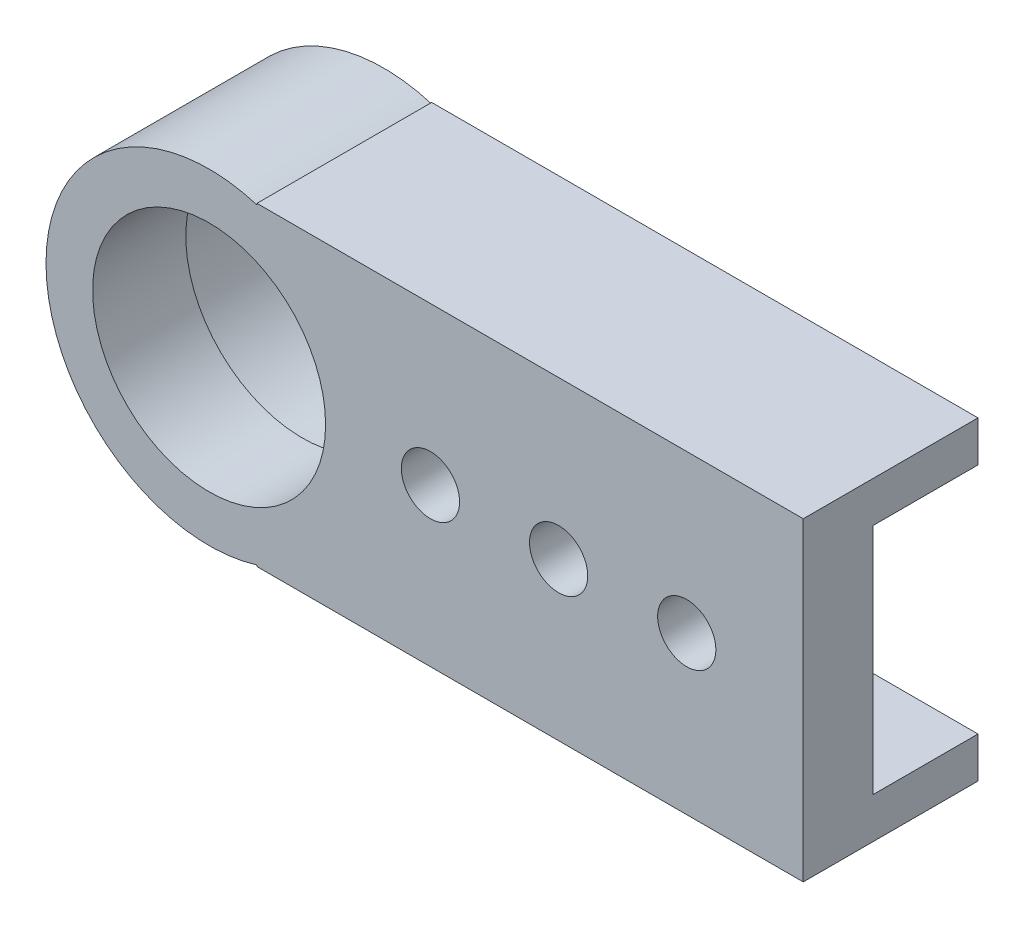
SolidWorks part; units mm, degrees
ref_plane "前视基准面" through (0, 0, 0) normal (0, 0, 1) x (1, 0, 0)
ref_plane "上视基准面" through (0, 0, 0) normal (0, 1, 0) x (1, 0, 0)
ref_plane "右视基准面" through (0, 0, 0) normal (1, 0, 0) x (0, 0, -1)
sketch "草图1" plane through (0, 0, 0) normal (0, 0, 1) x (1, 0, 0)
  line L1 (20, -10) -> (-20, -10)
  line L2 (20, -10) -> (20, 10)
  line L3 (20, 10) -> (-20, 10)
  line L4 (-20, -10) -> (-20, 10)
  line L5 (20, -10) -> (-20, 10) construction
  line L6 (20, 10) -> (-20, -10) construction
  point P0 (0, 0)
  dimension "D1" = 40
  dimension "D2" = 20
extrude "凸台-拉伸1" add sketch "草图1" along normal blind 6
sketch "草图2" plane through (0, 0, 6) normal (0, 0, 1) x (1, 0, 0)
  line L0 (20, -10) -> (20, 10) construction
  circle A0 centre (10, 0) radius 2.5
  circle A1 centre (-1, 0) radius 2.5
  circle A2 centre (-12, 0) radius 2.5
  dimension "D1" = 10
  dimension "D2" = 5
  dimension "D3" = 3
extrude "切除-拉伸1" cut sketch "草图2" against normal through all
sketch "草图3" plane through (0, 0, 6) normal (0, 0, 1) x (1, 0, 0)
  line L0 (20, 13.5) -> (20, 10)
  line L1 (20, -13.5) -> (-26.894, -13.5)
  line L3 (20, 13.5) -> (-26.894, 13.5)
  line L4 (-20, 10) -> (-20, -10)
  line L5 (-20, -10) -> (20, -10)
  line L6 (20, -10) -> (20, 10)
  line L7 (20, 10) -> (-20, 10)
  line L8 (-20, 10) -> (-20, -10)
  line L9 (-20, -10) -> (20, -10)
  line L10 (20, -10) -> (20, 10)
  line L11 (20, 10) -> (-20, 10)
  line L12 (-26.894, -13.5) -> (-26.894, 13.5)
  line L13 (20, -10.0394) -> (-26.894, 13.5) construction
  line L14 (20, 10.0394) -> (-26.894, -13.5) construction
  line L15 (20, -10) -> (20, -13.5)
  circle A0 centre (-31, 0) radius 11
  circle A1 centre (-31, 0) radius 14
  point P2 (0, 0)
  line M10 (-20, 10) -> (-20, -10)
  line M11 (-20, -10) -> (20, -10)
  line M13 (20, 10) -> (-20, 10)
  dimension "D3" = 22
  dimension "D4" = 28
  dimension "D2" = 3.5
  dimension "D1" = 0
extrude "凸台-拉伸2" add sketch "草图3" against normal blind 15 contours L3 A1 L1 L12 A0 | A1 L1 L15 M11 M10 | L1 A1 L8 A0 L12 | L8 A1 L3 L12 A0 | L8 A1 | A1 L0 L3 M10 M13 region at (-1.9449, 11.7771, 6) region at (-1.9449, -11.7771, 6) region at (-23.0173, 9.0328, 6) region at (-27.2274, 11.7946, 6) region at (-18.7882, 0, 6) region at (-23.0173, -9.0328, 6)
sketch "草图5" plane through (0, 0, 6) normal (0, 0, 1) x (1, 0, 0)
  circle A0 centre (-31, 0) radius 10
  circle A1 centre (-31, 0) radius 11 construction
  circle A2 centre (-31, 0) radius 11
  dimension "D1" = 20
extrude "凸台-拉伸3" add sketch "草图5" against normal blind 8
sketch "草图6" plane through (0, 0, 6) normal (0, 0, 1) x (1, 0, 0)
  circle A0 centre (-31, 0) radius 8.5
  circle A1 centre (-31, 0) radius 10 construction
  circle A2 centre (-31, 0) radius 10
  dimension "D1" = 17
